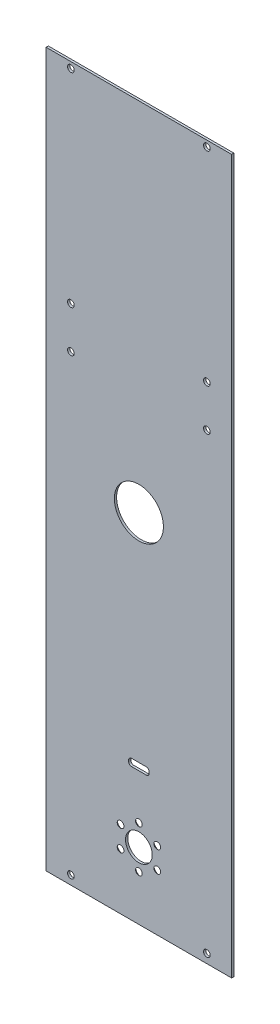
SolidWorks part; units mm, degrees
material "6061 Сплав"
ref_plane "Front Plane" through (0, 0, 0) normal (0, 0, 1) x (1, 0, 0)
ref_plane "Top Plane" through (0, 0, 0) normal (0, 1, 0) x (1, 0, 0)
ref_plane "Right Plane" through (0, 0, 0) normal (1, 0, 0) x (0, 0, -1)
sketch "Sketch1" plane through (0, 0, 0) normal (0, 0, 1) x (1, 0, 0)
  line L1 (41.6, -160) -> (-41.6, -160)
  line L2 (41.6, -160) -> (41.6, 160)
  line L3 (41.6, 160) -> (-41.6, 160)
  line L4 (-41.6, -160) -> (-41.6, 160)
  line L5 (41.6, -160) -> (-41.6, 160) construction
  line L6 (41.6, 160) -> (-41.6, -160) construction
  point P0 (0, 0)
  dimension "D1" = 83.2
  dimension "D2" = 320
extrude "Boss-Extrude1" add sketch "Sketch1" along normal blind 1
hole_wizard "Ø3.0 (3) Diameter Hole1" positions "Sketch3" profile "Sketch2" hole size "Ø3.0" standard "ANSI Metric"
sketch "Sketch3" plane through (0, 0, 1) normal (0, 0, 1) x (1, 0, 0)
  line L6 (-41.6, -160) -> (41.6, -160) construction
  line L9 (41.6, 160) -> (-41.6, 160) construction
  line L10 (0, 160) -> (0, 163.7587) construction
  line L11 (0, 160) -> (0, -152.1509) construction
  point P0 (-30.5, 66)
  point P2 (30.5, 66)
  point P15 (30.5, -156)
  point P17 (-30.5, -156)
  point P54 (-30.5, 157.3)
  point P56 (30.5, 157.3)
  point P58 (-30.5, 47.3)
  point P60 (30.5, 47.3)
  dimension "D2" = 4
  dimension "D3" = 2.7
  dimension "D4" = 4
  dimension "D5" = 30.5
  dimension "D6" = 30.5
  dimension "D7" = 94
  dimension "D8" = 30.5
  dimension "D9" = 2.7
  dimension "D10" = 94
  dimension "D11" = 30.5
  dimension "D12" = 30.5
  dimension "D13" = 30.5
  dimension "D14" = 30.5
  dimension "D15" = 30.5
  dimension "D16" = 112.7
  dimension "D17" = 112.7
sketch "Sketch2" plane through (-30.5, 66, 1) normal (1, 0, 0) x (0, -1, 0)
  line L0 (0, 0) -> (0, 1)
  line L1 (0, 1) -> (1.5, 1)
  line L2 (1.5, 1) -> (1.5, 0)
  line L5 (1.5, 0) -> (0, 0)
  line L10 (0, 1) -> (-1.5, 1) construction
  line L11 (0, -6.35) -> (0, 107.95) construction
  dimension "Hole Dia." = 3
  dimension "Hole Depth" = 1
  dimension "Drill Angle" = 180
sketch "Эскиз1" plane through (0, 0, 1) normal (0, 0, 1) x (1, 0, 0)
  circle A0 centre (0, 0) radius 11
extrude "Вырез-Вытянуть1" cut sketch "Эскиз1" against normal through all
sketch "Эскиз2" plane through (0, 0, 1) normal (0, 0, 1) x (1, 0, 0)
  line L0 (-41.6, -160) -> (41.6, -160) construction
  circle A0 centre (0, -130) radius 6
  dimension "D1" = 12
  dimension "D2" = 30
extrude "Вырез-Вытянуть2" cut sketch "Эскиз2" against normal blind 10
sketch "Эскиз3" plane through (0, 0, 1) normal (0, 0, 1) x (1, 0, 0)
  circle A0 centre (0, -130) radius 6 construction
  circle A1 centre (0, -130) radius 6 construction
  circle A2 centre (0, -120.5) radius 1.5
  dimension "D1" = 3
  dimension "D2" = 9.5
extrude "Вырез-Вытянуть3" cut sketch "Эскиз3" against normal blind 10
chamfer "Фаска1" distance 1 angle 45 1 edges at (1.5, -120.5, 0)
pattern_circular "Круговой массив1" count 6 over 360 about axis through (0, -130, -9) along (0, 0, 1) of "Вырез-Вытянуть3", "Фаска1"
sketch "Эскиз4" plane through (0, 0, 0) normal (0, 0, -1) x (-1, 0, 0)
  line L0 (0, 0) -> (0, -234.0626) construction
  line L3 (-3.3, -100.2966) -> (3.3, -100.2966)
  line L4 (-4.6, -98.9966) -> (-4.6, -98.3966)
  line L5 (-3.3, -97.0966) -> (3.3, -97.0966)
  line L6 (4.6, -98.9966) -> (4.6, -98.3966)
  line L7 (-4.6, -100.2966) -> (4.6, -97.0966) construction
  line L8 (-4.6, -97.0966) -> (4.6, -100.2966) construction
  arc A1 (-4.6, -98.9966) -> (-3.3, -100.2966) centre (-3.3, -98.9966) ccw
  arc A2 (3.3, -100.2966) -> (4.6, -98.9966) centre (3.3, -98.9966) ccw
  arc A3 (4.6, -98.3966) -> (3.3, -97.0966) centre (3.3, -98.3966) ccw
  arc A4 (-4.6, -98.3966) -> (-3.3, -97.0966) centre (-3.3, -98.3966) cw
  point P0 (0, -98.6966)
  point P5 (0, 0)
  dimension "D1" = 9.2
  dimension "D3" = 1.3
  dimension "D2" = 3.2
extrude "Вырез-Вытянуть4" cut sketch "Эскиз4" against normal blind 10
